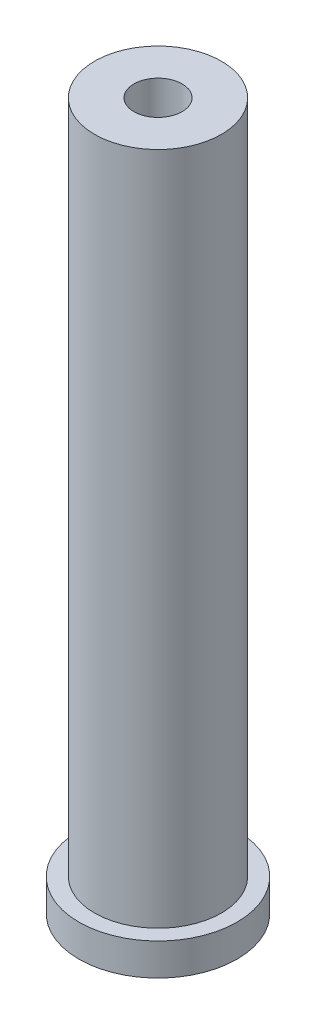
SolidWorks part; units mm, degrees
ref_plane "Ebene vorne" through (0, 0, 0) normal (0, 0, 1) x (1, 0, 0)
ref_plane "Ebene oben" through (0, 0, 0) normal (0, 1, 0) x (1, 0, 0)
ref_plane "Ebene rechts" through (0, 0, 0) normal (1, 0, 0) x (0, 0, -1)
sketch "Skizze1" plane through (0, 0, 0) normal (0, 1, 0) x (1, 0, 0)
  circle A0 centre (0, 0) radius 4.925
  dimension "D1" = 9.85
extrude "Aufsatz-Linear austragen1" add sketch "Skizze1" along normal blind 2
sketch "Skizze2" plane through (0, 2, 0) normal (0, 1, 0) x (1, 0, 0)
  circle A0 centre (0, 0) radius 3.95
  dimension "D1" = 7.9
extrude "Aufsatz-Linear austragen2" add sketch "Skizze2" along normal blind 42
sketch "Skizze3" plane through (0, 44, 0) normal (0, 1, 0) x (1, 0, 0)
  circle A0 centre (0, 0) radius 1.5
  dimension "D1" = 3
extrude "Schnitt-Linear austragen1" cut sketch "Skizze3" against normal blind 15
